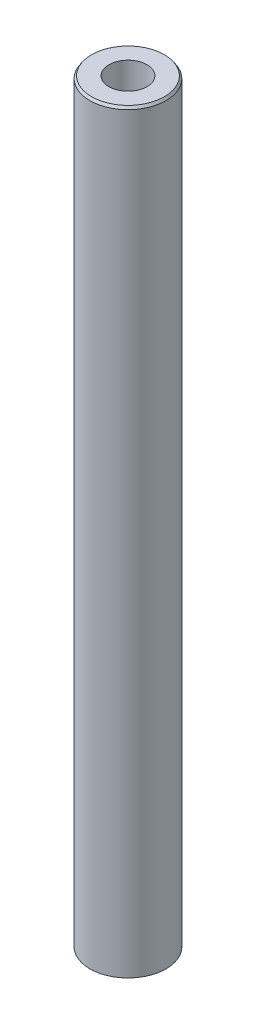
SolidWorks part; units mm, degrees
ref_plane "Front Plane" through (0, 0, 0) normal (0, 0, 1) x (1, 0, 0)
ref_plane "Top Plane" through (0, 0, 0) normal (0, 1, 0) x (1, 0, 0)
ref_plane "Right Plane" through (0, 0, 0) normal (1, 0, 0) x (0, 0, -1)
sketch "Sketch1" plane through (0, 0, 0) normal (0, 1, 0) x (1, 0, 0)
  circle A0 centre (0, 0) radius 12.5
  dimension "SHAFT_OD" = 25
extrude "Boss-Extrude1" add sketch "Sketch1" along normal blind 248.1536
sketch "Sketch2" plane through (0, 0, 0) normal (0, 1, 0) x (1, 0, 0)
  circle A0 centre (0, 0) radius 6.2485
  dimension "BORE_D" = 12.4969
extrude "Cut-Extrude1" cut sketch "Sketch2" along normal through all
chamfer "Chamfer1" distance 0.8287 angle 34.091 2 edges at (0, 248.1536, 12.5) (0, 0, 12.5) first distance on face at (0, 248.1536, 12.5) first distance on face at (0, 0, 6.2485)
